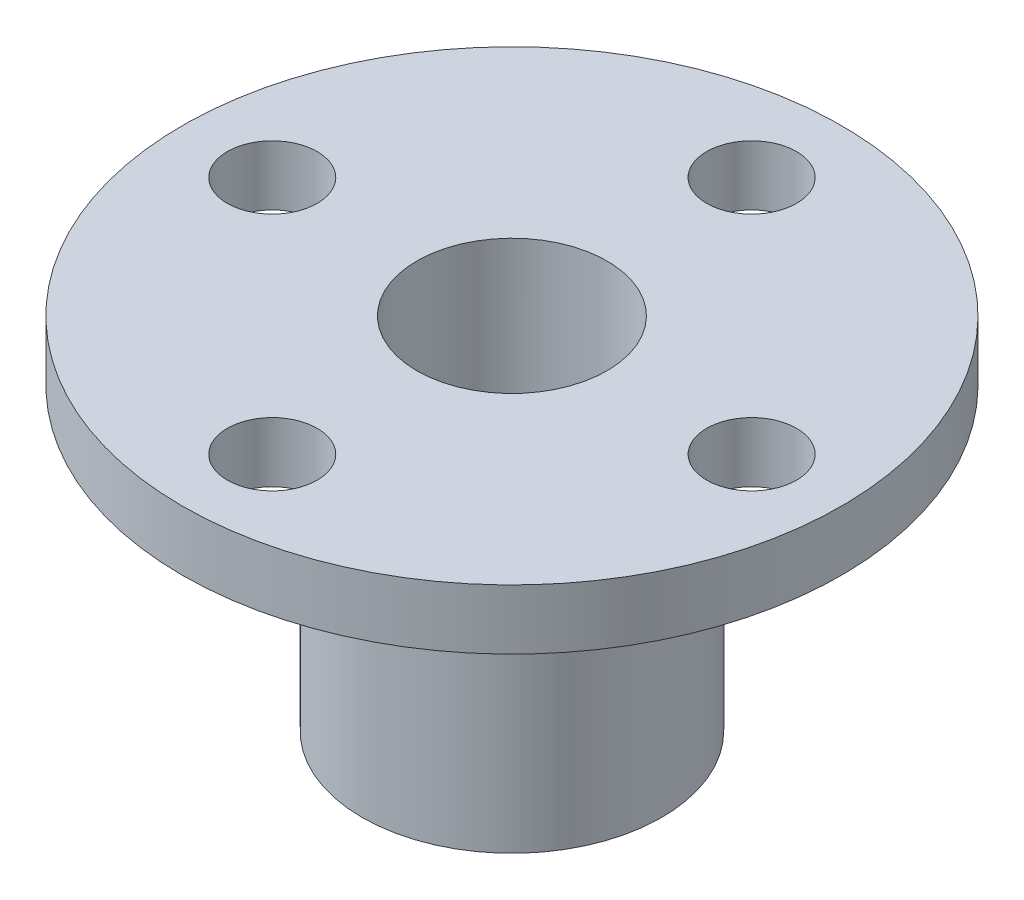
SolidWorks part; units mm, degrees
ref_plane "Front Plane" through (0, 0, 0) normal (0, 0, 1) x (1, 0, 0)
ref_plane "Top Plane" through (0, 0, 0) normal (0, 1, 0) x (1, 0, 0)
ref_plane "Right Plane" through (0, 0, 0) normal (1, 0, 0) x (0, 0, -1)
sketch "Sketch1" plane through (0, 0, 0) normal (0, 1, 0) x (1, 0, 0)
  circle A0 centre (0, 0) radius 3.175
  circle A1 centre (0, 0) radius 5
  dimension "D1" = 6.35
  dimension "D2" = 10
extrude "Boss-Extrude1" add sketch "Sketch1" along normal blind 12
sketch "Sketch2" plane through (0, 12, 0) normal (0, 1, 0) x (1, 0, 0)
  circle A0 centre (0, 0) radius 11
  circle A1 centre (0, 0) radius 3.175 construction
  circle A2 centre (0, 0) radius 3.175
  dimension "D1" = 22
extrude "Boss-Extrude2" add sketch "Sketch2" against normal blind 2
sketch "Sketch3" plane through (0, 12, 0) normal (0, 1, 0) x (1, 0, 0)
  line L0 (0, 11) -> (0, -11) construction
  circle A0 centre (0, 0) radius 8 construction
  circle A1 centre (0, 8) radius 1.5
  circle A2 centre (0, 0) radius 11 construction
  circle A3 centre (8, 0) radius 1.5
  circle A4 centre (0, -8) radius 1.5
  circle A5 centre (-8, 0) radius 1.5
  point P19 (0, 0)
  dimension "D1" = 16
  dimension "D2" = 3
  dimension "D3" = 4
extrude "Cut-Extrude1" cut sketch "Sketch3" against normal through all
ref_axis "Axis1" through (0, -0.6, 0) along (0, 1, 0)
ref_plane "Plane1" through (0, 0, 0) normal (0.7071, 0, 0.7071) x (0, 1, 0)
sketch "Sketch4" plane through (0, 0, 0) normal (0.7071, 0, 0.7071) x (0, 1, 0)
  line L1 (0, 0) -> (2, 0)
  circle A0 centre (3.5, 0) radius 1.5
  dimension "D1" = 3
  dimension "D2" = 2
extrude "Cut-Extrude2" cut sketch "Sketch4" against normal through all contours A0 region at (0, 3.5, 0)
ref_plane "Plane2" through (0, 0, 0) normal (0.7071, 0, -0.7071) x (0, 1, 0)
equation "\"plate_thickness\"= 2mm"
equation "\"D1@Boss-Extrude2\"=\"plate_thickness\""
equation "\"set screw diam\"= 3mm"
equation "\"D1@Sketch4\"=\"set screw diam\""
equation "\"set screw offset from end\"= 2mm"
equation "\"D2@Sketch4\"=\"set screw offset from end\""
